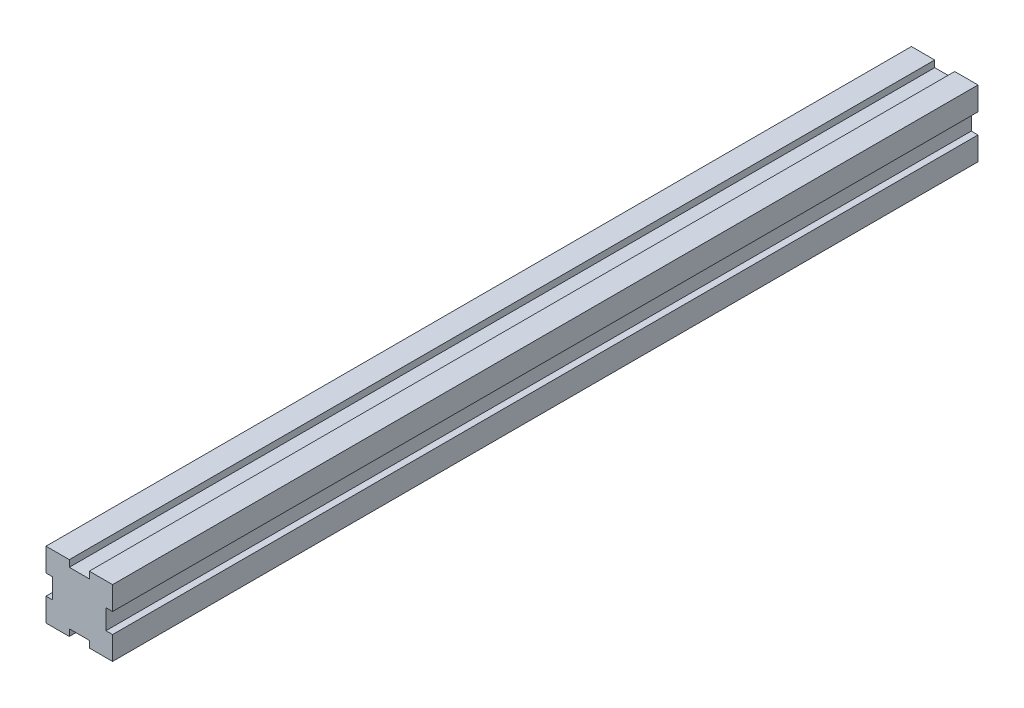
SolidWorks part; units mm, degrees
ref_plane "前视基准面" through (0, 0, 0) normal (0, 0, 1) x (1, 0, 0)
ref_plane "上视基准面" through (0, 0, 0) normal (0, 1, 0) x (1, 0, 0)
ref_plane "右视基准面" through (0, 0, 0) normal (1, 0, 0) x (0, 0, -1)
sketch "草图1" plane through (0, 0, 0) normal (0, 0, 1) x (1, 0, 0)
  line L0 (0, -13) -> (0, -20)
  line L1 (0, 0) -> (7, 0)
  line L2 (0, 0) -> (0, -7)
  line L3 (0, -20) -> (7, -20)
  line L4 (20, 0) -> (20, -7)
  line L5 (20, -7) -> (18, -7)
  line L6 (13, -20) -> (20, -20)
  line L7 (20, -13) -> (18, -13)
  line L8 (18, -7) -> (18, -13)
  line L9 (0, -7) -> (2, -7)
  line L10 (13, 0) -> (20, 0)
  line L11 (0, -13) -> (2, -13)
  line L12 (2, -7) -> (2, -13)
  line L13 (20, -13) -> (20, -20)
  line L14 (7, 0) -> (7, -2)
  line L15 (7, -2) -> (13, -2)
  line L16 (13, 0) -> (13, -2)
  line L17 (0, -7) -> (0, -13) construction
  line L18 (7, -20) -> (7, -18)
  line L19 (7, -18) -> (13, -18)
  line L20 (13, -20) -> (13, -18)
  line L21 (7, 0) -> (13, 0) construction
  line L22 (20, -7) -> (20, -13) construction
  line L23 (13, -20) -> (7, -20) construction
  point P21 (10, 0)
  point P22 (10, -2)
  point P23 (10, -18)
  point P24 (2, -10)
  point P25 (18, -10)
  point P26 (0, -10)
  dimension "D1" = 20
  dimension "D2" = 20
  dimension "D3" = 6
  dimension "D4" = 6
  dimension "D5" = 6
  dimension "D6" = 6
  dimension "D7" = 10
  dimension "D8" = 10
  dimension "D9" = 2
  dimension "D10" = 2
  dimension "D11" = 2
  dimension "D12" = 2
extrude "凸台-拉伸1" add sketch "草图1" along normal blind 260
